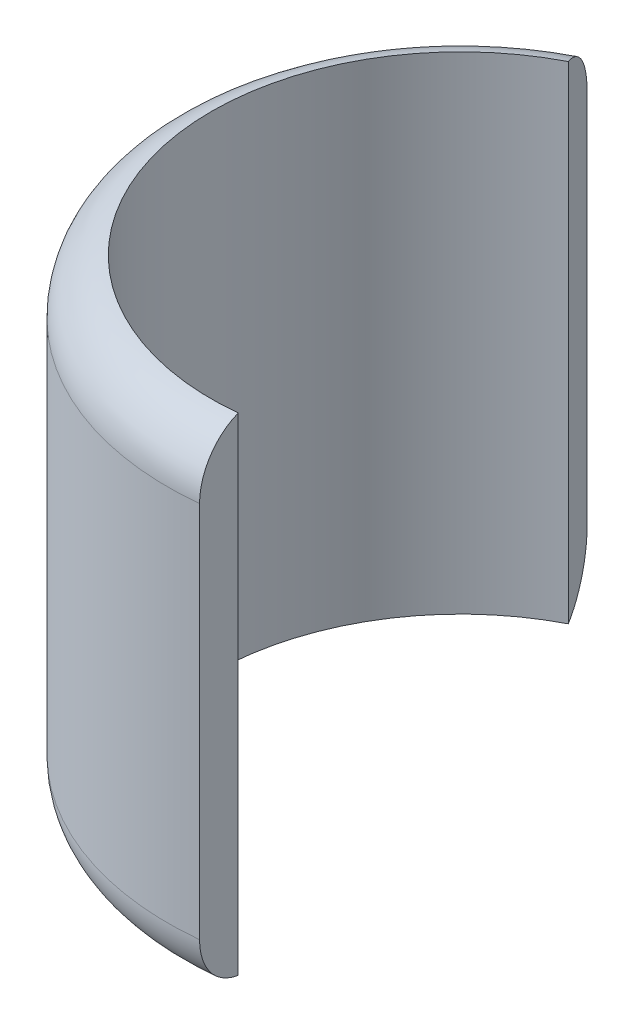
SolidWorks part; units mm, degrees
ref_plane "Front Plane" through (0, 0, 0) normal (0, 0, 1) x (1, 0, 0)
ref_plane "Top Plane" through (0, 0, 0) normal (0, 1, 0) x (1, 0, 0)
ref_plane "Right Plane" through (0, 0, 0) normal (1, 0, 0) x (0, 0, -1)
sketch "Sketch1" plane through (0, 0, 0) normal (0, 1, 0) x (1, 0, 0)
  line L0 (0, 0) -> (4.3085, -41.8795)
  line L1 (0, 0) -> (-24.9991, 48.6559)
  circle A0 centre (0, 0) radius 19.96
  circle A1 centre (0, 0) radius 17
  dimension "D1" = 158.68
extrude "Boss-Extrude1" add sketch "Sketch1" along normal blind 33.23 contours A1 L1 A0 L0 region at (1.4569, 0, 18.4277)
fillet "Fillet1" radius 3.83 2 edges at (-19.1347, 0, 5.6802) (-19.1347, 33.23, 5.6802)
